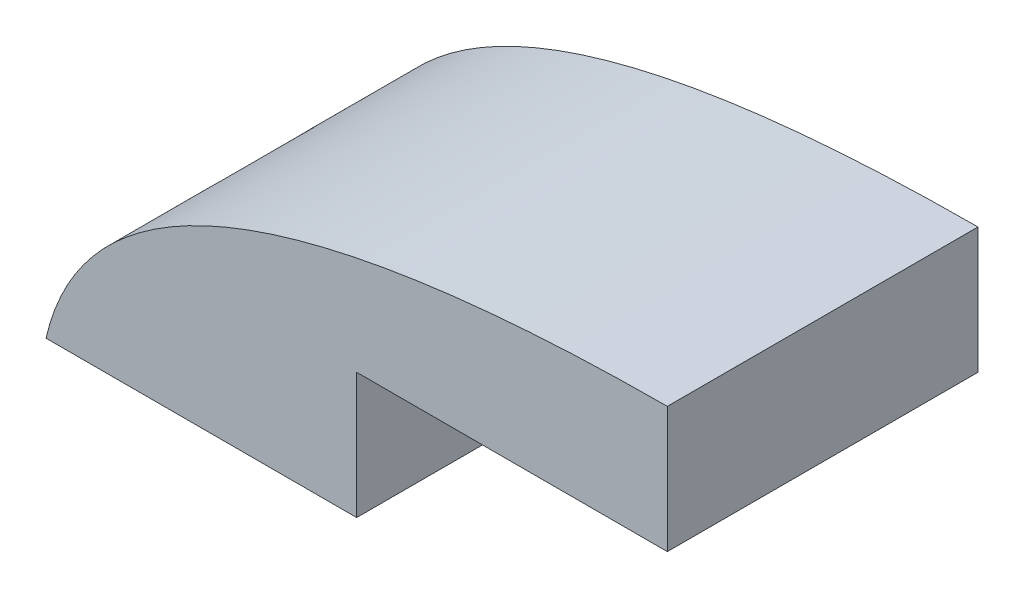
SolidWorks part; units mm, degrees
ref_plane "Front Plane" through (0, 0, 0) normal (0, 0, 1) x (1, 0, 0)
ref_plane "Top Plane" through (0, 0, 0) normal (0, 1, 0) x (1, 0, 0)
ref_plane "Right Plane" through (0, 0, 0) normal (1, 0, 0) x (0, 0, -1)
sketch "Sketch2" plane through (0, 0, 0) normal (0, 1, 0) x (1, 0, 0)
  line L1 (0, 0) -> (7.9, 0)
  line L2 (0, 0) -> (0, 7.9)
  line L3 (0, 7.9) -> (7.9, 7.9)
  line L4 (7.9, 0) -> (7.9, 7.9)
  dimension "D1" = 7.9
  dimension "D2" = 7.9
extrude "Boss-Extrude1" add sketch "Sketch2" along normal blind 3.2
sketch "Sketch3" plane through (0, 3.2, 0) normal (0, 1, 0) x (1, 0, 0)
  line L1 (7.9, 7.9) -> (15.8, 7.9)
  line L2 (7.9, 7.9) -> (7.9, 0)
  line L3 (7.9, 0) -> (15.8, 0)
  line L4 (15.8, 7.9) -> (15.8, 0)
  dimension "D1" = 7.9
extrude "Boss-Extrude2" add sketch "Sketch3" along normal blind 3.2 separate body
sketch "Sketch4" plane through (0, 0, -7.9) normal (0, 0, -1) x (-1, 0, 0)
  line L0 (-15.8, 6.4) -> (0, 6.4)
  line L1 (0, 6.4) -> (0, 0)
  spline S0 degree 2 poles (-15.8, 6.4) (-1.4724, 6.3571) (0, 0) knots 0 0 0 1 1 1
  point P1 (-7.4097, 2.5464)
  point P2 (-4.238, 4.5318)
  point P4 (-3.8627, 4.4107)
sketch "Sketch7" plane through (7.9, 0, 0) normal (-1, 0, 0) x (0, 0, 1)
  line L1 (0, 3.2) -> (-7.9, 3.2)
  line L2 (0, 3.2) -> (0, 6.4)
  line L3 (0, 6.4) -> (-7.9, 6.4)
  line L4 (-7.9, 3.2) -> (-7.9, 6.4)
extrude "Boss-Extrude5" add sketch "Sketch7" along normal blind 7.2
extrude "Cut-Extrude2" cut sketch "Sketch4" against normal blind 8.2
